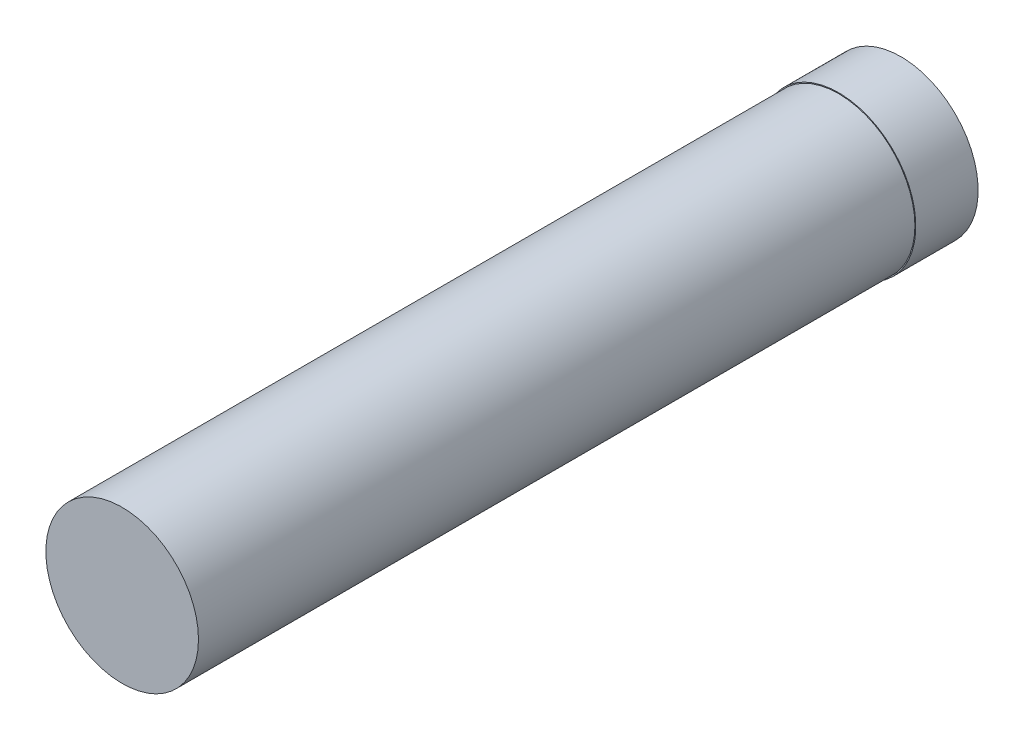
SolidWorks part; units mm, degrees
ref_plane "Front Plane" through (0, 0, 0) normal (0, 0, 1) x (1, 0, 0)
ref_plane "Top Plane" through (0, 0, 0) normal (0, 1, 0) x (1, 0, 0)
ref_plane "Right Plane" through (0, 0, 0) normal (1, 0, 0) x (0, 0, -1)
sketch "Sketch1" plane through (0, 0, 0) normal (0, 0, 1) x (1, 0, 0)
  circle A0 centre (0, 0) radius 2.45
  dimension "D1" = 4.9
extrude "Boss-Extrude1" add sketch "Sketch1" along normal blind 15 and the other way blind 10
sketch "Sketch2" plane through (0, 0, 0) normal (0, 0, 1) x (1, 0, 0)
  circle A0 centre (0, 0) radius 2.5 construction
  dimension "D1" = 5
sketch "Sketch3" plane through (0, 0, -10) normal (0, 0, -1) x (-1, 0, 0)
  circle A0 centre (0, 0) radius 2.48
  dimension "D1" = 4.96
extrude "Boss-Extrude2" add sketch "Sketch3" against normal blind 2
